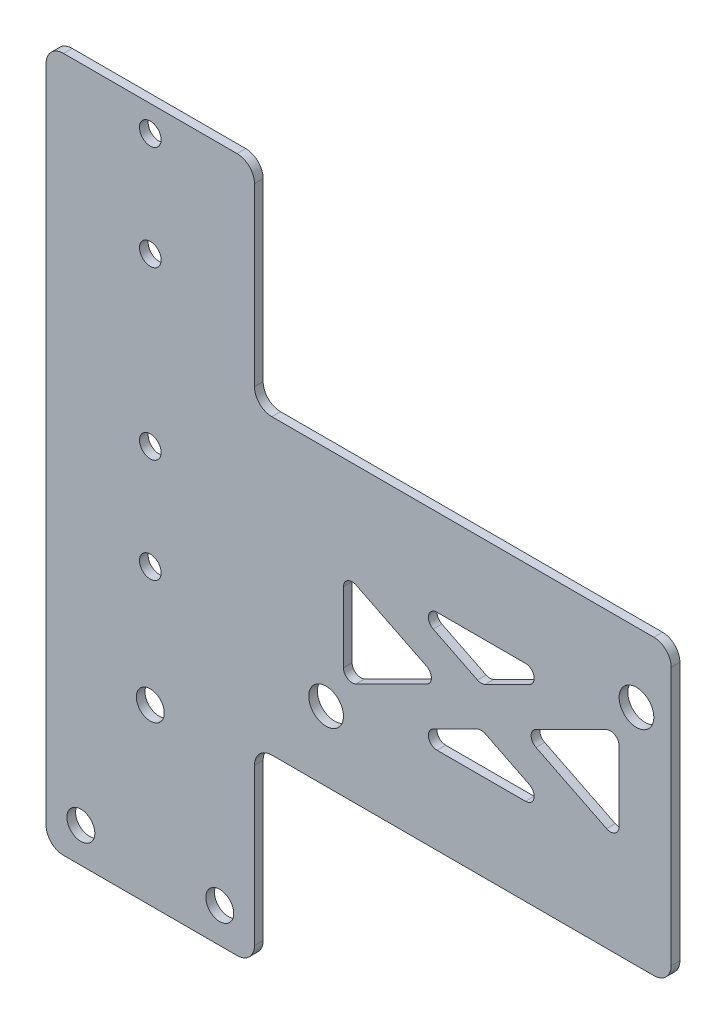
SolidWorks part; units mm, degrees
ref_plane "Front Plane" through (0, 0, 0) normal (0, 0, 1) x (1, 0, 0)
ref_plane "Top Plane" through (0, 0, 0) normal (0, 1, 0) x (1, 0, 0)
ref_plane "Right Plane" through (0, 0, 0) normal (1, 0, 0) x (0, 0, -1)
sketch "Sketch1" plane through (0, 0, 0) normal (0, 0, 1) x (1, 0, 0)
  line L1 (-19.05, 63.5) -> (19.05, 63.5)
  line L2 (-19.05, 63.5) -> (-19.05, -63.5)
  line L3 (-19.05, -63.5) -> (19.05, -63.5)
  line L4 (19.05, 63.5) -> (19.05, -63.5)
  line L5 (-19.05, 63.5) -> (19.05, -63.5) construction
  line L6 (-19.05, -63.5) -> (19.05, 63.5) construction
  line L7 (19.05, 25.019) -> (95.25, 25.019)
  line L8 (19.05, 25.019) -> (19.05, -28.575)
  line L9 (19.05, -28.575) -> (95.25, -28.575)
  line L10 (95.25, 25.019) -> (95.25, -28.575)
  circle A0 centre (32.1437, -15.875) radius 3.175
  circle A1 centre (88.9, 12.319) radius 3.175
  point P0 (0, 0)
  dimension "D7" = 6.35
  dimension "D1" = 34.925
  dimension "D2" = 38.1
  dimension "D3" = 76.2
  dimension "D4" = 127
  dimension "D5" = 6.35
  dimension "D6" = 12.7
  dimension "D8" = 12.7
  dimension "D9" = 56.7563
  dimension "D10" = 63.3733
extrude "Boss-Extrude1" add sketch "Sketch1" along normal mid plane 1.5875 contours L10 L7 L4 L9 A1 A0 | L4 L1 L2 L3 region at (0, 0, 0) region at (57.0969, -1.778, 0)
sketch "Sketch2" plane through (0, 0, 0.7937) normal (0, 0, 1) x (1, 0, 0)
  line L1 (-12.7, -57.15) -> (12.7, -57.15) construction
  line L2 (-19.05, -63.5) -> (19.05, -63.5) construction
  circle A0 centre (-12.7, -57.15) radius 2.5527
  circle A1 centre (12.7, -57.15) radius 2.5527
  circle A2 centre (0, -31.75) radius 2.5527
  circle A3 centre (0, -9.8425) radius 1.9812
  circle A4 centre (0, 9.2075) radius 1.9812
  circle A5 centre (0, 39.6875) radius 1.9812
  circle A6 centre (0, 58.7375) radius 1.9812
  point P14 (0, -57.15)
  dimension "D1" = 3.9624
  dimension "D2" = 5.1054
  dimension "D3" = 25.4
  dimension "D4" = 25.4
  dimension "D5" = 21.9075
  dimension "D6" = 6.35
  dimension "D7" = 19.05
  dimension "D8" = 30.48
  dimension "D9" = 19.05
extrude "Cut-Extrude1" cut sketch "Sketch2" against normal through all
fillet "Fillet1" radius 3.175 8 edges at (95.25, -28.575, 0) (19.05, -28.575, 0) (19.05, -63.5, 0) (-19.05, -63.5, 0) (-19.05, 63.5, 0) (19.05, 63.5, 0) (95.25, 25.019, 0) (19.05, 25.019, 0)
sketch "Sketch3" plane through (0, 0, 0.7937) normal (0, 0, 1) x (1, 0, 0)
  line L0 (35.3187, -12.7) -> (85.725, -12.7)
  line L1 (32.1437, 12.319) -> (88.9, 12.319)
  line L2 (32.1437, 12.319) -> (32.1437, -15.875)
  line L3 (32.1437, -15.875) -> (88.9, -15.875)
  line L4 (88.9, 12.319) -> (88.9, -15.875)
  line L5 (32.1437, 12.319) -> (88.9, -15.875) construction
  line L6 (32.1437, -15.875) -> (88.9, 12.319) construction
  line L7 (85.725, 9.144) -> (85.725, -12.7)
  line L8 (35.3187, 9.144) -> (85.725, 9.144)
  line L9 (35.3187, 9.144) -> (35.3187, -12.7)
  line L10 (30.7312, 9.4755) -> (87.4875, -18.7185)
  line L11 (33.5562, -18.7185) -> (90.3125, 9.4755)
  line L12 (33.5562, 15.1625) -> (90.3125, -13.0315)
  line L13 (30.7312, -13.0315) -> (87.4875, 15.1625)
  circle A0 centre (32.1437, -15.875) radius 3.175 construction
  point P0 (60.5219, -1.778)
  dimension "D1" = 3.175
  dimension "D2" = 3.175
  dimension "D3" = 3.175
extrude "Cut-Extrude2" cut sketch "Sketch3" against normal through all contours L12 L13 L8 | L9 L13 L10 | L11 L0 L10 | L11 L12 L7 region at (60.5219, -10.2411, 0.7937) region at (41.3409, -1.778, 0.7937) region at (79.7028, -1.778, 0.7937) region at (60.5219, 6.6851, 0.7937)
fillet "Fillet2" radius 1.5875 12 edges at (60.5219, -5.3232, 0) (75.3719, -12.7, 0) (75.3719, 9.144, 0) (45.6718, 9.144, 0) (60.5218, 1.7672, 0) (85.725, 7.1966, 0) (85.725, -10.7526, 0) (67.6585, -1.778, 0) (45.6718, -12.7, 0) (53.3852, -1.778, 0) (35.3187, 7.1966, 0) (35.3187, -10.7526, 0)
